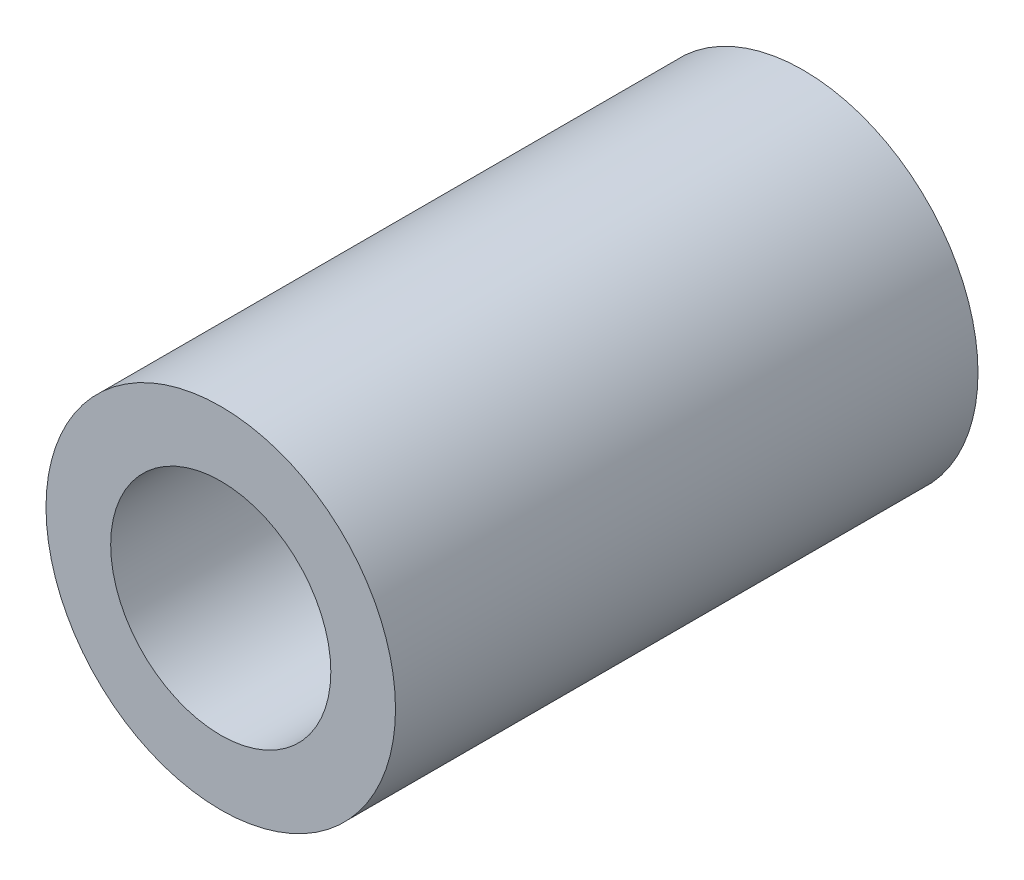
SolidWorks part; units mm, degrees
material "ABS"
ref_plane "Front Plane" through (0, 0, 0) normal (0, 0, 1) x (1, 0, 0)
ref_plane "Top Plane" through (0, 0, 0) normal (0, 1, 0) x (1, 0, 0)
ref_plane "Right Plane" through (0, 0, 0) normal (1, 0, 0) x (0, 0, -1)
sketch "Sketch1" plane through (0, 0, 0) normal (0, 0, 1) x (1, 0, 0)
  circle A0 centre (0, 0) radius 1.5
  circle A1 centre (0, 0) radius 2.3813
  dimension "D1" = 3
  dimension "D2" = 4.7625
extrude "Boss-Extrude1" add sketch "Sketch1" along normal mid plane 7.9375
